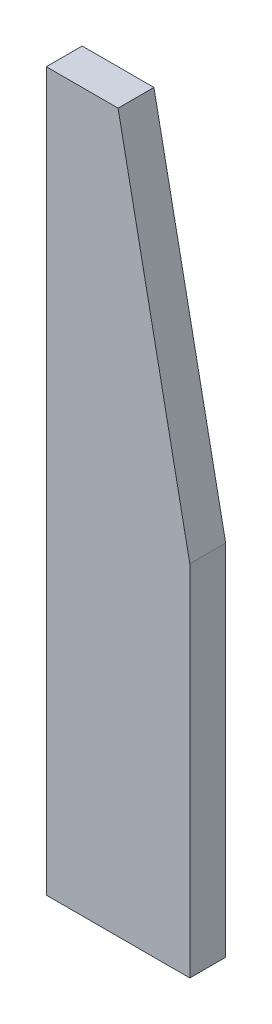
SolidWorks part; units mm, degrees
material "6061 Alloy"
ref_plane "Front Plane" through (0, 0, 0) normal (0, 0, 1) x (1, 0, 0)
ref_plane "Top Plane" through (0, 0, 0) normal (0, 1, 0) x (1, 0, 0)
ref_plane "Right Plane" through (0, 0, 0) normal (1, 0, 0) x (0, 0, -1)
sketch "Sketch1" plane through (0, 0, 0) normal (1, 0, 0) x (0, 0, -1)
  line L1 (-3.175, -63.5) -> (3.175, -63.5)
  line L2 (-3.175, -63.5) -> (-3.175, 63.5)
  line L3 (-3.175, 63.5) -> (3.175, 63.5)
  line L4 (3.175, -63.5) -> (3.175, 63.5)
  line L5 (-3.175, -63.5) -> (3.175, 63.5) construction
  line L6 (-3.175, 63.5) -> (3.175, -63.5) construction
  point P0 (0, 0)
  dimension "D1" = 6.35
  dimension "D2" = 127
extrude "Boss-Extrude1" add sketch "Sketch1" along normal blind 25.4
hole_wizard "M2.5x0.45 Tapped Hole1" positions "Sketch2" profile "Sketch3" tap size "M2.5x0.45" standard "ANSI Metric"
sketch "Sketch2" plane through (0, 0, 0) normal (-1, 0, 0) x (0, 0, 1)
  line L0 (0, -53.5) -> (0, -26.75)
  line L1 (0, -26.75) -> (0, 0)
  line L2 (0, 0) -> (0, 26.75)
  line L3 (0, 26.75) -> (0, 53.5)
  line L5 (-3.175, 63.5) -> (3.175, 63.5) construction
  point P0 (0, 53.5)
  point P2 (0, 26.75)
  point P4 (0, 0)
  point P7 (0, -26.75)
  point P9 (0, -53.5)
  point P22 (0, -57.6843)
  dimension "D1" = 10
sketch "Sketch3" plane through (0, 53.5, 0) normal (0, 1, 0) x (0, 0, 1)
  line L0 (0, 0) -> (0, 6.9659)
  line L1 (0, 6.9659) -> (1.025, 6.35)
  line L2 (1.025, 6.35) -> (1.025, 0)
  line L5 (1.025, 0) -> (0, 0)
  line L10 (0, 6.9659) -> (-1.025, 6.35) construction
  line L11 (0, -6.35) -> (0, 107.95) construction
  dimension "Tap Drill Dia." = 2.05
  dimension "Tap Drill Depth" = 6.35
  dimension "Drill Angle" = 118
cosmetic thread "Hole Thread1" parameters "D1"=5, "D2"=2.5
cosmetic thread "Hole Thread2" parameters "D1"=5, "D2"=2.5
cosmetic thread "Hole Thread3" parameters "D1"=5, "D2"=2.5
cosmetic thread "Hole Thread4" parameters "D1"=5, "D2"=2.5
cosmetic thread "Hole Thread5" parameters "D1"=5, "D2"=2.5
sketch "Sketch4" plane through (0, 0, 3.175) normal (0, 0, 1) x (1, 0, 0)
  line L0 (12.7, 63.5) -> (25.4, 0)
  line L1 (25.4, 63.5) -> (0, 63.5) construction
  line L2 (25.4, 63.5) -> (25.4, -63.5) construction
  line M3 (25.4, -63.5) -> (25.4, 63.5)
  line M4 (25.4, 63.5) -> (0, 63.5)
extrude "Cut-Extrude1" cut sketch "Sketch4" against normal through all and the other way through all contours L0 M4 M3 region at (21.1667, 42.3333, 3.175)
